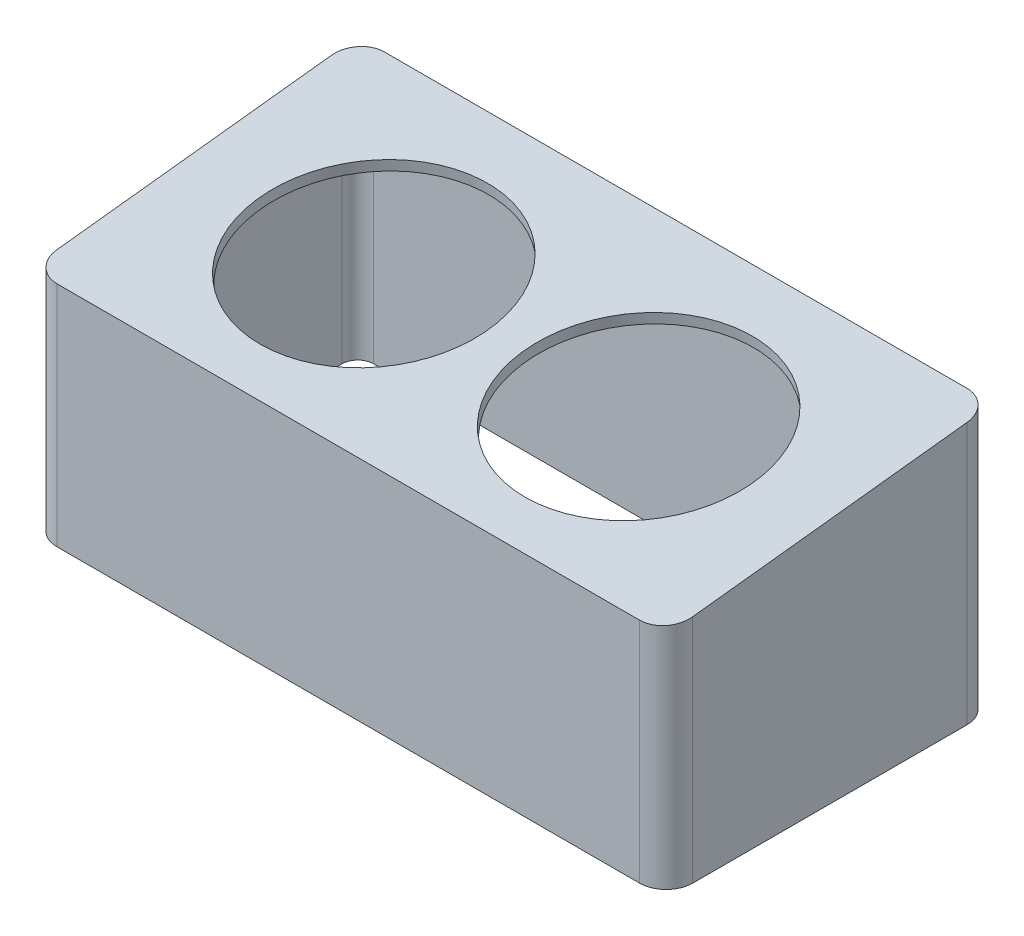
SolidWorks part; units mm, degrees
ref_plane "前视基准面" through (0, 0, 0) normal (0, 0, 1) x (1, 0, 0)
ref_plane "上视基准面" through (0, 0, 0) normal (0, 1, 0) x (1, 0, 0)
ref_plane "右视基准面" through (0, 0, 0) normal (1, 0, 0) x (0, 0, -1)
other "Configuration Table"
sketch "草图3" plane through (0, 0, 0) normal (0, 1, 0) x (1, 0, 0)
  line L1 (-35.2583, 30.485) -> (74.7417, 30.485)
  line L2 (-40.2583, 25.485) -> (-40.2583, -26.315)
  line L3 (-35.2583, -31.315) -> (74.7417, -31.315)
  line L4 (79.7417, 25.485) -> (79.7417, -26.315)
  arc A0 (-40.2583, -26.315) -> (-35.2583, -31.315) centre (-35.2583, -26.315) ccw
  arc A1 (74.7417, -31.315) -> (79.7417, -26.315) centre (74.7417, -26.315) ccw
  arc A2 (74.7417, 30.485) -> (79.7417, 25.485) centre (74.7417, 25.485) cw
  arc A3 (-35.2583, 30.485) -> (-40.2583, 25.485) centre (-35.2583, 25.485) ccw
  point P6 (-40.2583, -31.315)
  point P11 (79.7417, 30.485)
  point P14 (-40.2583, 30.485)
  dimension "D3" = 5
  dimension "D1" = 61.8
  dimension "D2" = 120
extrude "凸台-拉伸6" add sketch "草图3" along normal blind 50 contours A3 L2 A0 L3 A1 L4 A2 L1
sketch "草图4" plane through (79.7417, 0, 0) normal (1, 0, 0) x (0, 0, -1)
  line L0 (30.485, 50) -> (-31.315, 43)
  line L1 (-31.315, 50) -> (-31.315, 0) construction
  line L2 (-31.315, 43) -> (-31.315, 50)
  line L3 (-31.315, 50) -> (30.485, 50)
  dimension "D1" = 7
extrude "切除-拉伸1" cut sketch "草图4" against normal through all both and the other way through all contours L3 L0 L2
sketch "草图5" plane through (0, 45.9574, 5.2055) normal (0, 0.9936, 0.1125) x (1, 0, 0)
  line L0 (19.7417, -26.2764) -> (19.7417, 35.9188) construction
  line L1 (-35.2583, -26.2764) -> (74.7417, -26.2764) construction
  line L2 (-35.2583, 35.9188) -> (74.7417, 35.9188) construction
  circle A0 centre (44.7417, 3.7236) radius 21.6018
  circle A1 centre (-5.2583, 3.7236) radius 21.6018
  dimension "D1" = 50
  dimension "D2" = 30
extrude "切除-拉伸2" cut sketch "草图5" against normal through all contours A1 | A0
sketch "草图7" plane through (0, 0, 0) normal (0, -1, 0) x (-1, 0, 0)
  line L1 (33.2583, -29.315) -> (-72.7417, -29.315)
  line L2 (38.2583, -24.315) -> (38.2583, 23.485)
  line L3 (33.2583, 28.485) -> (-72.7417, 28.485)
  line L4 (-77.7417, -24.315) -> (-77.7417, 23.485)
  line L5 (35.2583, -31.315) -> (-74.7417, -31.315) construction
  line L6 (35.2583, 30.485) -> (-74.7417, 30.485) construction
  line L7 (40.2583, 25.485) -> (40.2583, -26.315) construction
  line L8 (-79.7417, 25.485) -> (-79.7417, -26.315) construction
  arc A1 (38.2583, 23.485) -> (33.2583, 28.485) centre (33.2583, 23.485) ccw
  arc A2 (-72.7417, 28.485) -> (-77.7417, 23.485) centre (-72.7417, 23.485) ccw
  arc A3 (-72.7417, -29.315) -> (-77.7417, -24.315) centre (-72.7417, -24.315) cw
  arc A4 (33.2583, -29.315) -> (38.2583, -24.315) centre (33.2583, -24.315) ccw
  point P14 (38.2583, 28.485)
  point P19 (-77.7417, -29.315)
  point P22 (38.2583, -29.315)
  dimension "D7" = 5
  dimension "D1" = 116
  dimension "D2" = 57.8
  dimension "D3" = 2
  dimension "D4" = 2
  dimension "D5" = 2
  dimension "D6" = 2
shell "抽壳3" thickness 2 removed face at (-5.2583, 0, 17.9926) removed face at (44.7417, 0, 17.9926) removed face at (-5.2583, 0, 17.9926)
